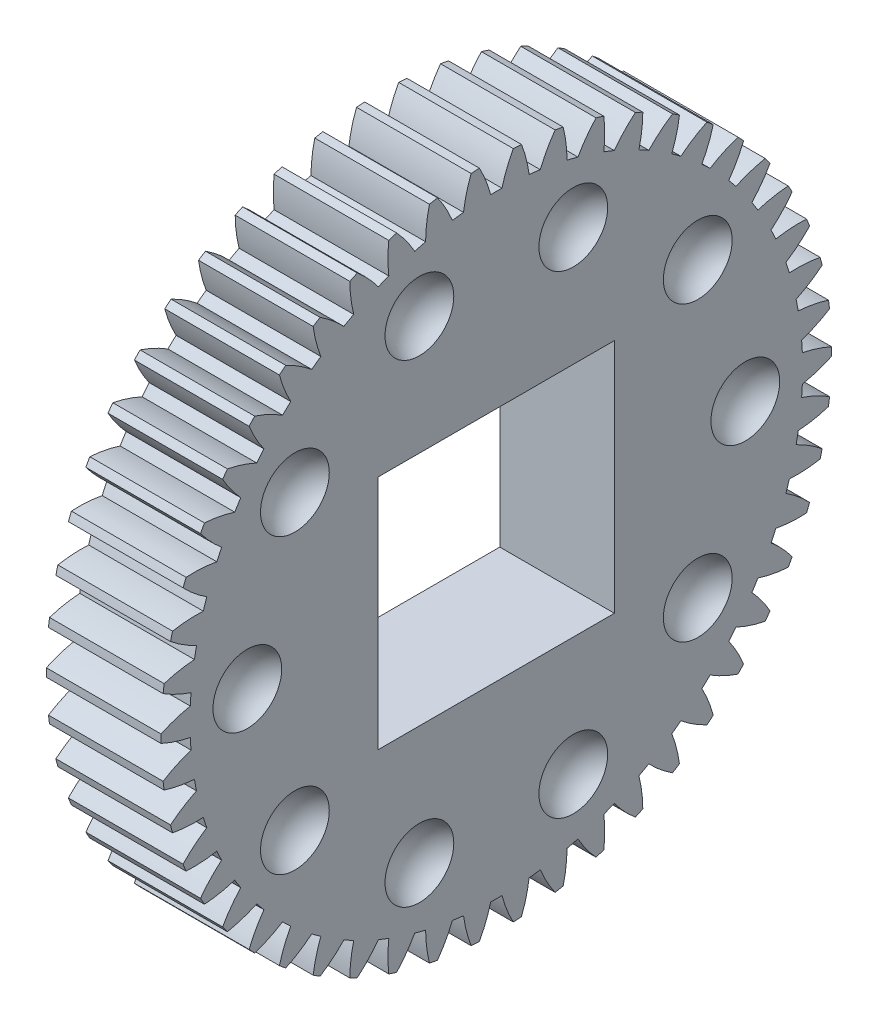
SolidWorks part; units mm, degrees
ref_plane "Plane1" through (0, 0, 0) normal (0, 0, 1) x (1, 0, 0)
ref_plane "Plane2" through (0, 0, 0) normal (0, 1, 0) x (1, 0, 0)
ref_plane "Plane3" through (0, 0, 0) normal (1, 0, 0) x (0, 0, -1)
sketch "HoldingSke" plane through (0, 0, 0) normal (0, 1, 0) x (1, 0, 0)
  line L0 (0, 0) -> (0.5714, -0.6809)
  line L1 (-15, 0) -> (100, 0) construction
  line L2 (0, 0) -> (-2.1039, 2.3779)
  line L3 (0, 0) -> (-11.863, 4.5341)
  line L4 (0, 0) -> (5.5511, 6.6156)
  line L5 (0, 0) -> (-46.8476, -17.4728)
  line L6 (0, 0) -> (-8.2896, -5.593)
  line L7 (-2.1039, 2.3779) -> (8.6586, 51.2059)
  line L8 (-76.2, 54.61) -> (-76.1, 54.61)
  line L9 (-71.009, 38.7566) -> (-53.1078, 45.2721)
  line L10 (-76.2, 71.12) -> (104.1128, 71.12)
  line L11 (0, 0) -> (-10, 0)
  line L12 (-76.2, 101.6) -> (-76.158, 101.6)
  line L13 (24.9733, 27.94) -> (52.9518, 28.4284)
  line L14 (24.9733, 27.94) -> (24.9743, 27.94)
  line L15 (24.9733, 27.94) -> (100.4006, 29.5858)
  line L16 (-63.627, -1.125) -> (-12.827, -1.125)
  circle A0 centre (0, 0) radius 0.4
  circle A1 centre (0, 0) radius 26.7178
  circle A2 centre (0, 0) radius 37.5
  circle A3 centre (0, 0) radius 0.4
  dimension "MHD" = 53.4355
  dimension "Hub_dia" = 75
  dimension "Bore" = 0.8
  dimension "MBD" = 0.8
  dimension "Num_teeth" = 50
  dimension "Pitch" = 0.8889
  dimension "Overall_len" = 50
  dimension "Show_teeth" = 50
  dimension "Thickness" = 10
  dimension "OAL" = 50.0001
  dimension "T_dim" = 0.1
  dimension "Ap" = 20
  dimension "H" = 19.05
  dimension "Pitch_radius" = 180.3128
  dimension "Width" = 10
  dimension "Backlash" = 0.042
  dimension "Addendum_fac" = 1
  dimension "Dedendum_fac" = 1.25
  dimension "Clearance_fac" = 0.25
  dimension "Dedendum_add" = 0.001
  dimension "Module" = 1.125
sketch "BasProSke" plane through (0, 0, 0) normal (0, 1, 0) x (1, 0, 0)
  line L0 (-10, 0) -> (60, 0) construction
  line L1 (0, 0) -> (0, 29.25)
  line L2 (0, 0) -> (10, 0)
  line L3 (10, 0) -> (10, 29.25)
  line L4 (10, 29.25) -> (0, 29.25)
  dimension "Thickness" = 10
  dimension "Diameter" = 58.5
revolve "Base-Revolve" add sketch "BasProSke" angle 360 about L0
sketch "TooCutSke" plane through (0, 0, 0) normal (1, 0, 0) x (0, 0, -1)
  line L1 (0, 0) -> (0, 107) construction
  line L2 (0, 0) -> (-0.9569, 28.1087) construction
  line L3 (0, 0) -> (-3.5305, 56.1157) construction
  line L4 (-0.9569, 28.1087) -> (-1.7653, 28.0579) construction
  arc A0 (0.4912, 26.7132) -> (-0.4912, 26.7132) centre (0, 0) ccw
  arc A1 (1.4926, 29.2373) -> (-1.4926, 29.2373) centre (0, 0) ccw
  circle A2 centre (0, 0) radius 28.125 construction
  circle A3 centre (0, 0) radius 26.4289 construction
  arc A4 (-0.4912, 26.7132) -> (-1.4926, 29.2373) centre (-11.3725, 23.8569) ccw
  arc A5 (1.4926, 29.2373) -> (0.4912, 26.7132) centre (11.3725, 23.8569) ccw
  dimension "Root_dia" = 53.4355
  dimension "Overcut_dia" = 58.5508
  dimension "Pitch_dia" = 56.25
  dimension "Base_dia" = 52.8577
  dimension "Flank_rad" = 11.25
  dimension "Half_ang" = 3.6
  dimension "Half_CT" = 0.8099
extrude "ToothCut" cut sketch "TooCutSke" along normal through all
fillet "Breaks" [suppressed] radius 0.0225 tangent propagation no
fillet "RootFillets" [suppressed] radius 0.2823
pattern_circular "TeethCuts" count 50 every 7.2 about axis through (-10, 0, 0) along (1, 0, 0) of "ToothCut", "RootFillets", "Breaks"
sketch "HubNeaOneSke" plane through (0, 0, 0) normal (-1, 0, 0) x (0, 0, 1)
  circle A0 centre (0, 0) radius 26.7178
  dimension "Diameter" = 53.4355
extrude "HubNearOne" [suppressed] add sketch "HubNeaOneSke" along normal blind 40.0001
sketch "HubNeaBotSke" plane through (0, 0, 0) normal (-1, 0, 0) x (0, 0, 1)
  circle A0 centre (0, 0) radius 26.7178
  dimension "Diameter" = 53.4355
extrude "HubNearBoth" [suppressed] add sketch "HubNeaBotSke" along normal blind 20
ref_plane "FarPln" through (10, 0, 0) normal (1, 0, 0) x (0, 0, -1)
sketch "HubFarSke" plane through (10, 0, 0) normal (1, 0, 0) x (0, 0, -1)
  circle A0 centre (0, 0) radius 26.7178
  dimension "Diameter" = 53.4355
extrude "HubFar" [suppressed] add sketch "HubFarSke" along normal blind 20
sketch "BorSke" plane through (0, 0, 0) normal (1, 0, 0) x (0, 0, -1)
  circle A0 centre (0, 0) radius 0.4
  dimension "Diameter" = 0.8
extrude "Bore" cut sketch "BorSke" along normal mid plane 100.0001
sketch "KeySke" plane through (0, 0, 0) normal (1, 0, 0) x (0, 0, -1)
  line L0 (-0.05, 0) -> (-0.05, 0.5)
  line L1 (-0.05, 0.5) -> (0.05, 0.5)
  line L2 (0.05, 0.5) -> (0.05, 0)
  line L3 (0, 0) -> (0, 34) construction
  line L4 (-0.05, 0) -> (0.05, 0)
  dimension "Offset" = 0.5
  dimension "Width" = 0.1
extrude "Keyway" [suppressed] cut sketch "KeySke" along normal mid plane 100.0001
pattern_circular "Keyway2" [suppressed] count 2 every 90 about axis through (-10, 0, 0) along (1, 0, 0) reverse direction yes
sketch "Sketch1" plane through (10, 0, 0) normal (1, 0, 0) x (0, 0, -1)
  circle A0 centre (0, 0) radius 26.7178 construction
  circle A1 centre (0, 0) radius 21.7177 construction
  circle A2 centre (-21.7177, 0) radius 3
  circle A3 centre (-17.57, 12.7654) radius 3
  circle A4 centre (-6.7112, 20.6548) radius 3
  circle A5 centre (6.7112, 20.6548) radius 3
  circle A6 centre (17.57, 12.7654) radius 3
  circle A7 centre (21.7177, 0) radius 3
  circle A8 centre (17.57, -12.7654) radius 3
  circle A9 centre (6.7112, -20.6548) radius 3
  circle A10 centre (-6.7112, -20.6548) radius 3
  circle A11 centre (-17.57, -12.7654) radius 3
  point P27 (0, 0)
  dimension "D2" = 6
  dimension "D1" = 5
  dimension "D3" = 10
extrude "Cut-Extrude1" cut sketch "Sketch1" against normal blind 2
fillet "Fillet1" radius 3.23 10 edges at (8, -20.6548, 3.7112) (8, -12.7654, 14.57) (8, 0, 18.7177) (8, 12.7654, 14.57) (8, 20.6548, 3.7112) (8, 20.6548, -9.7112) (8, 12.7654, -20.57) (8, 0, -24.7177) (8, -12.7654, -20.57) (8, -20.6548, -9.7112)
sketch "Sketch2" plane through (0, 0, 0) normal (-1, 0, 0) x (0, 0, 1)
  circle A0 centre (0, 0) radius 26.7177 construction
  circle A1 centre (0, 0) radius 21.7177 construction
  circle A2 centre (0, 0) radius 24.7177
  circle A3 centre (0, 0) radius 18.7177
  dimension "D1" = 5
  dimension "D2" = 3
  dimension "D3" = 3
extrude "Cut-Extrude2" cut sketch "Sketch2" against normal blind 2
fillet "Fillet2" radius 3.25 2 edges at (2, 0, 18.7177) (2, 0, 24.7177)
sketch "Sketch3" plane through (10, 0, 0) normal (1, 0, 0) x (0, 0, -1)
  line L1 (10.3, -10.3) -> (-10.3, -10.3)
  line L2 (10.3, -10.3) -> (10.3, 10.3)
  line L3 (10.3, 10.3) -> (-10.3, 10.3)
  line L4 (-10.3, -10.3) -> (-10.3, 10.3)
  line L5 (10.3, -10.3) -> (-10.3, 10.3) construction
  line L6 (10.3, 10.3) -> (-10.3, -10.3) construction
  point P0 (0, 0)
  dimension "D1" = 20.6
  dimension "D2" = 20.6
extrude "Cut-Extrude3" cut sketch "Sketch3" against normal through all
equation "' \"Module@HoldingSke\" = 6.35"
equation "' \"Num_teeth@HoldingSke\" = 12"
equation "' \"Ap@HoldingSke\" =  20"
equation "' \"Ap@HoldingSke\" = 20"
equation "' \"Width@HoldingSke\" = 0.5 * 25.4"
equation "' \"Hub_dia@HoldingSke\"= 1 * 25.4"
equation "' \"Hub_dia@HoldingSke\" = 1 * 25.4"
equation "' \"Overall_len@HoldingSke\" = 1.0 * 25.4"
equation "' \"Bore@HoldingSke\" = 0.75 * 25.4"
equation "' \"T_dim@HoldingSke\" = 0.1 * 25.4"
equation "' \"Width@KeySke\" = 0.25 * 25.4"
equation "' \"Show_teeth@HoldingSke\" = 13"
equation "' \"Backlash@HoldingSke\" = 0.009 * 25.4"
equation "' \"Addendum_fac@HoldingSke\" = 1.0"
equation "' \"Dedendum_fac@HoldingSke\" = 1.25"
equation "' \"Dedendum_add@HoldingSke\" = 0.00005 * 25.4"
equation "' \"Clearance_fac@HoldingSke\" = 0.25"
equation "\"Pitch@HoldingSke\" = 1 / \"Module@HoldingSke\""
equation "\"Overcut_dia@TooCutSke\" = (\"Num_teeth@HoldingSke\" + 2 * \"Addendum_fac@HoldingSke\") / \"Pitch@HoldingSke\" + 0.002 * 25.4"
equation "\"Pitch_dia@TooCutSke\" = \"Num_teeth@HoldingSke\" / \"Pitch@HoldingSke\""
equation "\"Base_dia@TooCutSke\" = \"Num_teeth@HoldingSke\" / \"Pitch@HoldingSke\" * cos((\"Ap@HoldingSke\"  * 3.14159265 / 180))"
equation "\"Root_dia@TooCutSke\" = (\"Num_teeth@HoldingSke\" + 2) / \"Pitch@HoldingSke\" - 2 * (\"Addendum_fac@HoldingSke\" + \"Dedendum_fac@HoldingSke\") / \"Pitch@HoldingSke\" - \"Dedendum_add@HoldingSke\" * 2"
equation "\"Half_ang@TooCutSke\" = 180 / \"Num_teeth@HoldingSke\""
equation "\"Half_CT@TooCutSke\" = \"Num_teeth@HoldingSke\" / \"Pitch@HoldingSke\" * sin((3.14159265 / 2 / \"Num_teeth@HoldingSke\")) / 2 - 7 * \"Backlash@HoldingSke\" / 4"
equation "\"Flank_rad@TooCutSke\" = \"Num_teeth@HoldingSke\" / \"Pitch@HoldingSke\" / 5"
equation "\"Radius@RootFillets\" = \"Clearance_fac@HoldingSke\" / \"Pitch@HoldingSke\" + \"Dedendum_add@HoldingSke\""
equation "\"Break_rad@Breaks\" = 0.02 / \"Pitch@HoldingSke\""
equation "\"Thickness@HoldingSke\" = \"Width@HoldingSke\""
equation "\"OAL@HoldingSke\" = \"Thickness@HoldingSke\""
equation "\"MHD@HoldingSke\" = (\"Num_teeth@HoldingSke\" + 2) / \"Pitch@HoldingSke\" - 2 * (\"Addendum_fac@HoldingSke\" + \"Dedendum_fac@HoldingSke\")  / \"Pitch@HoldingSke\" - \"Dedendum_add@HoldingSke\" * 2"
equation "\"MBD@HoldingSke\" = (\"Num_teeth@HoldingSke\" + 2) / \"Pitch@HoldingSke\" - 2 * (\"Addendum_fac@HoldingSke\" + \"Dedendum_fac@HoldingSke\")  / \"Pitch@HoldingSke\" - \"Dedendum_add@HoldingSke\" * 2 - 0.002 * 25.4"
equation "\"MHD@HoldingSke\" = ((sgn( \"MHD@HoldingSke\" - \"Hub_dia@HoldingSke\" )-1)*( \"MHD@HoldingSke\" - \"Hub_dia@HoldingSke\" ))/-2+ \"Hub_dia@HoldingSke\""
equation "\"MBD@HoldingSke\" = ((sgn( \"MBD@HoldingSke\" - \"Bore@HoldingSke\" )-1)*( \"MBD@HoldingSke\" - \"Bore@HoldingSke\" ))/-2+ \"Bore@HoldingSke\""
equation "\"OAL@HoldingSke\" = ((sgn( \"OAL@HoldingSke\" - \"Overall_len@HoldingSke\" )+1)*( \"OAL@HoldingSke\" - \"Overall_len@HoldingSke\" ))/2 + \"Overall_len@HoldingSke\" + 0.000002 * 25.4"
equation "\"Num_teeth@TeethCuts\" = int( \"Show_teeth@HoldingSke\" ) + 1"
equation "\"Num_teeth@TeethCuts\" = ((sgn( \"Num_teeth@TeethCuts\" - \"Num_teeth@HoldingSke\" )-1)*( \"Num_teeth@TeethCuts\" - \"Num_teeth@HoldingSke\" ))/-2+ \"Num_teeth@HoldingSke\""
equation "\"Num_teeth@TeethCuts\" = ((sgn( \"Num_teeth@TeethCuts\" - 2.0)+1)*( \"Num_teeth@TeethCuts\" - 2.0))/2 +2.0"
equation "\"Angle@TeethCuts\" = 360.0 / \"Num_teeth@HoldingSke\""
equation "\"Diameter@BasProSke\" = (\"Num_teeth@HoldingSke\" + 2 * \"Addendum_fac@HoldingSke\") / \"Pitch@HoldingSke\""
equation "\"Thickness@BasProSke\"  = \"Thickness@HoldingSke\""
equation "' \"Fillet_rad@BasProSke\" =  \"Thickness@HoldingSke\" * 0.05"
equation "' \"Fillet_rad@BasProSke\" = \"Thickness@HoldingSke\" * 0.05"
equation "\"MHD@HoldingSke\" = ((sgn( \"MHD@HoldingSke\" - \"Root_dia@TooCutSke\" )-1)*( \"MHD@HoldingSke\" - \"Root_dia@TooCutSke\" ))/-2+ \"Root_dia@TooCutSke\""
equation "\"Diameter@HubNeaOneSke\" = \"MHD@HoldingSke\""
equation "\"Length@HubNearOne\" = \"OAL@HoldingSke\" - \"Thickness@BasProSke\""
equation "\"Diameter@HubNeaBotSke\" = \"MHD@HoldingSke\""
equation "\"Length@HubNearBoth\" = ( \"OAL@HoldingSke\" - \"Thickness@BasProSke\" ) / 2.0"
equation "\"Thickness@FarPln\" = \"Thickness@BasProSke\""
equation "\"Diameter@HubFarSke\" = \"MHD@HoldingSke\""
equation "\"Length@HubFar\" = ( \"OAL@HoldingSke\" - \"Thickness@BasProSke\" ) / 2.0"
equation "\"Diameter@BorSke\" = \"MBD@HoldingSke\""
equation "\"D1@Bore\" = \"OAL@HoldingSke\" * 2.0"
equation "\"D1@Keyway\" = \"OAL@HoldingSke\" * 2.0"
equation "\"Offset@KeySke\" = \"T_dim@HoldingSke\" + \"MBD@HoldingSke\" / 2.0"
